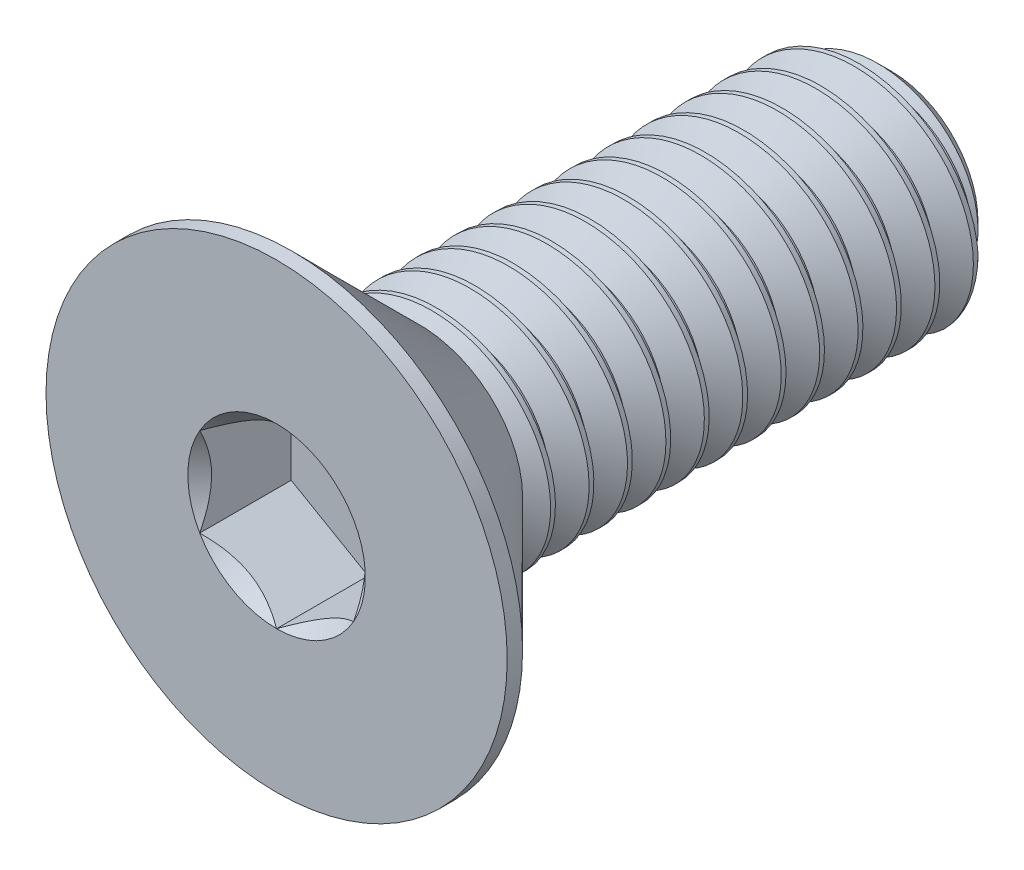
SolidWorks part; units mm, degrees
ref_plane "Front" through (0, 0, 0) normal (0, 0, 1) x (1, 0, 0)
ref_plane "Top" through (0, 0, 0) normal (0, 1, 0) x (1, 0, 0)
ref_plane "Right" through (0, 0, 0) normal (1, 0, 0) x (0, 0, -1)
sketch "Sketch1" plane through (0, 0, 0) normal (1, 0, 0) x (0, 0, -1)
  line L0 (0, 3) -> (0.2, 3) construction
  line L1 (0.2, 3) -> (1.7, 1.5) construction
  line L2 (0, 1.5) -> (8, 1.5)
  line L3 (8, 1.5) -> (8, 0)
  line L4 (8, 0) -> (0, 0)
  line L5 (0, 0) -> (0, 3) construction
  line L6 (0, 3) -> (0, -3) construction
  line L7 (8, 1.5) -> (8, -1.5) construction
  line L8 (0, -3) -> (0.2, -3) construction
  line L9 (0.2, -3) -> (1.7, -1.5) construction
  line L11 (0, 1.5) -> (0, 0)
  line L12 (1.7, 1.5) -> (1.7, 0) construction
  dimension "Head Ht" = 1.7
  dimension "Head Dia" = 6
  dimension "Dia" = 3
  dimension "Lg" = 8
  dimension "Head Angle" = 90
revolve "Revolve1" add sketch "Sketch1" angle 360 mid plane about L4
sketch "Sketch3" plane through (0, 0, -8) normal (0, 0, -1) x (-1, 0, 0)
  circle A0 centre (0, 0) radius 1.5
curve "Helix/Spiral1" pitch 0.5 height 8 radius 1.5 centre (0, 0, -8) axis (0, 0, 1) start towards (0, 1, 0)
sketch "Sketch2" plane through (0, 0, 0) normal (1, 0, 0) x (0, 0, -1)
  line L0 (8, 1.5) -> (8.4375, 1.5)
  line L1 (8.4375, 1.5) -> (8.25, 1.1752)
  line L2 (8.25, 1.1752) -> (8.1875, 1.1752)
  line L3 (8.1875, 1.1752) -> (8, 1.5)
  line L4 (8.0938, 1.3376) -> (8.3437, 1.3376) construction
  dimension "D1" = 60
  dimension "D2" = 0.0625
  dimension "D3" = 0.25
chamfer "Chamfer1" distance 0.375 angle 45 1 edges at (0, 1.5, -8)
sweep "Cut-Sweep1" cut profiles "Sketch2" path "Helix/Spiral1" align with end faces yes
sketch "Sketch7" plane through (0, 0, 0) normal (1, 0, 0) x (0, 0, -1)
  line L0 (0, 3) -> (0.2, 3) construction
  line L1 (0.2, 3) -> (1.7, 1.5) construction
  line L2 (0, 3) -> (0.2, 3)
  line L3 (0.2, 3) -> (1.7, 1.5)
  line L4 (1.7, 1.5) -> (1.7, 0) construction
  line L5 (1.7, 1.5) -> (1.7, 0)
  line L7 (0, 0) -> (0, 3) construction
  line L8 (0, 0) -> (0, 3)
  line L9 (0, 0) -> (1.7, 0)
  line L10 (3.3, 0) -> (-3.3, 0) construction
revolve "Revolve2" add sketch "Sketch7" angle 360 mid plane about L9
ref_plane "Plane1" through (0, 0, -1.7) normal (0, 0, 1) x (1, 0, 0)
sketch "Sketch8" plane through (0, 0, -1.7) normal (0, 0, 1) x (1, 0, 0)
  circle A0 centre (0, 0) radius 1.5
extrude "Boss-Extrude1" add sketch "Sketch8" against normal through all draft 45
sketch "Sketch5" plane through (0, 0, 0) normal (0, 0, 1) x (1, 0, 0)
  line L1 (1, -0.5774) -> (1, 0.5774)
  line L2 (1, 0.5774) -> (0, 1.1547)
  line L3 (0, 1.1547) -> (-1, 0.5774)
  line L4 (-1, 0.5774) -> (-1, -0.5774)
  line L5 (-1, -0.5774) -> (0, -1.1547)
  line L6 (0, -1.1547) -> (1, -0.5774)
  circle A0 centre (0, 0) radius 1 construction
  dimension "Hex" = 2
extrude "Cut-Extrude2" cut sketch "Sketch5" against normal blind 1.19
sketch "Sketch6" plane through (0, 0, 0) normal (0, 0, 1) x (1, 0, 0)
  circle A0 centre (0, 0) radius 1.1547
extrude "Cut-Extrude3" cut sketch "Sketch6" against normal blind 1.19 draft 45
sketch "Sketch9" [suppressed] plane through (0, 0, -5.5) normal (0, 0, 1) x (1, 0, 0)
  circle A1 centre (0, 0) radius 5
  circle A2 centre (0, 0) radius 5
  point P0 (0, 5)
  dimension "D1" = 0
extrude "Boss-Extrude2" [suppressed] add sketch "Sketch9" against normal offset from surface (18.5 mm away) 26 up to face at (0, 1.125, -8)
fillet "Fillet1" [suppressed] radius 0.3
sketch "Sketch10" plane through (0, 0, 0) normal (1, 0, 0) x (0, 0, -1)
  line L0 (8, 1.5) -> (8, -1.5) construction
  point P0 (7.25, -1.5)
  dimension "D1" = 0.75
equation "\"D3@Helix/Spiral1\" = \"Lg@Sketch1\""
equation "\"D2@Sketch2\" = \"D4@Helix/Spiral1\" * .125"
equation "\"D3@Sketch2\" = \"D4@Helix/Spiral1\" * .5"
equation "\"D1@Chamfer1\" = \"D4@Helix/Spiral1\" * .75"
equation "\"D1@Cut-Extrude2\" = \"Head Ht@Sketch1\" * .7"
equation "\"D1@Sketch10\" = \"D4@Helix/Spiral1\" * 1.5"
equation "\"D1@Cut-Extrude3\" = \"D1@Cut-Extrude2\""
equation "\"D1@Fillet1\" = \"Dia@Sketch1\" * .1"
